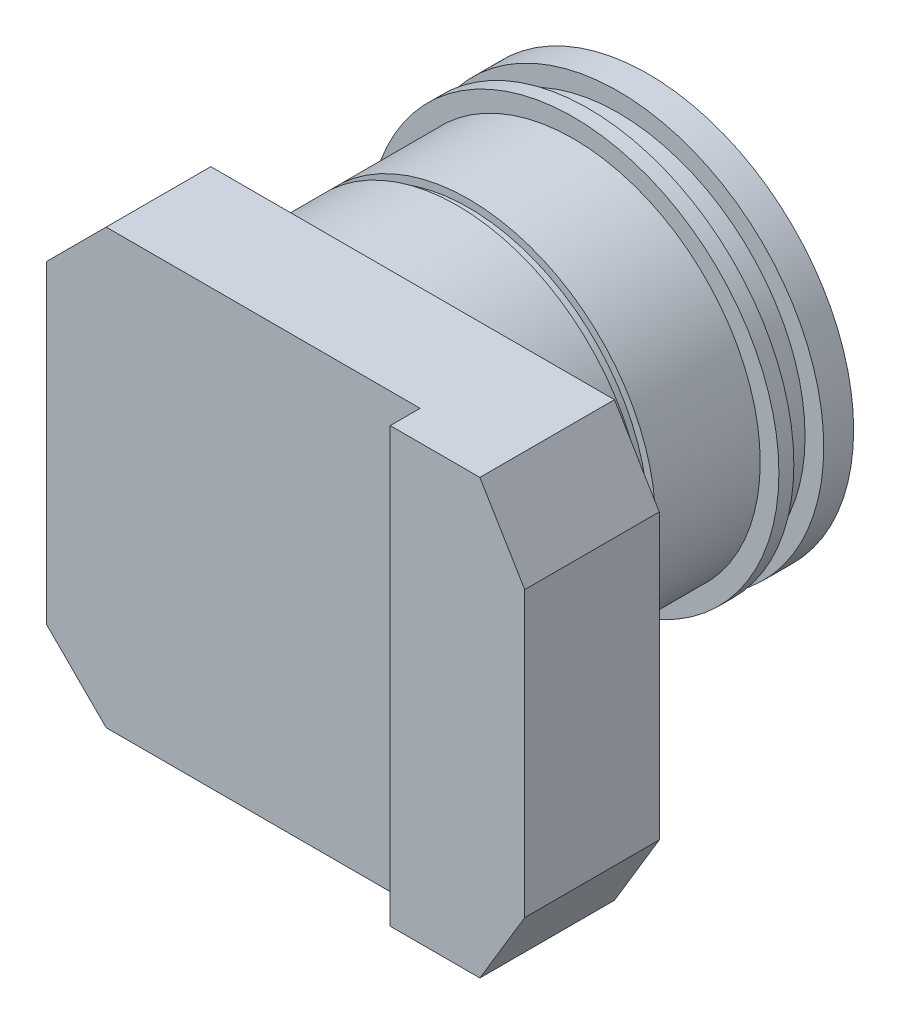
SolidWorks part; units mm, degrees
ref_plane "Front Plane" through (0, 0, 0) normal (0, 0, 1) x (1, 0, 0)
ref_plane "Top Plane" through (0, 0, 0) normal (0, 1, 0) x (1, 0, 0)
ref_plane "Right Plane" through (0, 0, 0) normal (1, 0, 0) x (0, 0, -1)
sketch "Sketch1" plane through (0, 0, 0) normal (0, 0, 1) x (1, 0, 0)
  line L1 (-17, 14.5) -> (17, 14.5)
  line L2 (-17, 14.5) -> (-17, -14.5)
  line L3 (-17, -14.5) -> (17, -14.5)
  line L4 (17, 14.5) -> (17, -14.5)
  line L5 (-17, 14.5) -> (17, -14.5) construction
  line L6 (-17, -14.5) -> (17, 14.5) construction
  point P0 (0, 0)
  dimension "D1" = 34
  dimension "D2" = 29
extrude "Boss-Extrude1" add sketch "Sketch1" along normal mid plane 7 contours L2 L3 L4 L1
sketch "Sketch2" plane through (0, 0, 3.5) normal (0, 0, 1) x (1, 0, 0)
  line L0 (-17, -14.5) -> (17, -14.5) construction
  line L1 (17, 14.5) -> (8, 14.5)
  line L2 (17, 14.5) -> (17, -14.5)
  line L3 (17, -14.5) -> (8, -14.5)
  line L4 (8, 14.5) -> (8, -14.5)
  dimension "D1" = 9
extrude "Boss-Extrude2" add sketch "Sketch2" along normal blind 2
sketch "Sketch3" plane through (0, 0, -3.5) normal (0, 0, -1) x (-1, 0, 0)
  line L0 (-14, -14.5) -> (-17, -9.5)
  line L1 (17, -14.5) -> (-17, -14.5) construction
  line L2 (-17, 14.5) -> (-17, -14.5) construction
  line L3 (-17, -9.5) -> (-17, -14.5)
  line L4 (-17, -14.5) -> (-14, -14.5)
  line L5 (13, -14.5) -> (17, -10.5)
  line L6 (17, 14.5) -> (17, -14.5) construction
  line L7 (17, -10.5) -> (17, -14.5)
  line L8 (17, -14.5) -> (13, -14.5)
  line L9 (17, 10.5) -> (13, 14.5)
  line L10 (17, 14.5) -> (-17, 14.5) construction
  line L11 (13, 14.5) -> (17, 14.5)
  line L12 (17, 14.5) -> (17, 10.5)
  line L13 (-17, 9.5) -> (-14, 14.5)
  line L14 (-14, 14.5) -> (-17, 14.5)
  line L15 (-17, 14.5) -> (-17, 9.5)
  dimension "D1" = 3
  dimension "D2" = 5
  dimension "D3" = 4
  dimension "D4" = 4
  dimension "D5" = 4
  dimension "D6" = 4
extrude "Cut-Extrude1" cut sketch "Sketch3" against normal through all
sketch "Sketch4" plane through (0, 0, 0) normal (0, 1, 0) x (1, 0, 0)
  line L0 (-17, 3.5) -> (-4.5, 3.5)
  line L1 (-17, 3.5) -> (-17, 11.5)
  line L2 (-17, 11.5) -> (-16.5, 11.5)
  line L3 (-16.5, 11.5) -> (-16.5, 12.25)
  line L4 (-16.5, 12.25) -> (-17, 12.25)
  line L5 (-17, 12.25) -> (-17, 19.25)
  line L6 (-17, 19.25) -> (-18.25, 19.25)
  line L7 (-18.25, 19.25) -> (-18.25, 20.25)
  line L8 (-18.25, 20.25) -> (-17, 20.25)
  line L9 (-17, 20.25) -> (-17, 22.25)
  line L10 (-17, 22.25) -> (-18.25, 22.25)
  line L11 (-18.25, 22.25) -> (-18.25, 24.25)
  line L12 (-18.25, 24.25) -> (-4.5, 24.25)
  line L13 (-17, 3.5) -> (8, 3.5) construction
  line L14 (-13, -3.5) -> (8, -3.5) construction
  line L15 (-4.5, 24.25) -> (-4.5, 3.5) construction
  line L16 (-4.5, 3.5) -> (-4.5, 24.25)
  dimension "D1" = 8
  dimension "D2" = 27.75
  dimension "D3" = 2
  dimension "D4" = 1
  dimension "D5" = 2
  dimension "D6" = 7
  dimension "D7" = 13.75
  dimension "D8" = 0.5
revolve "Revolve1" add sketch "Sketch4" angle 360 about L16
sketch "Sketch5" plane through (0, 0, -24.25) normal (0, 0, -1) x (-1, 0, 0)
  circle A0 centre (4.5, 0) radius 9.75
  circle A2 centre (4.5, 0) radius 13.75 construction
  dimension "D1" = 4
extrude "Cut-Extrude2" cut sketch "Sketch5" against normal blind 5 draft 45
sketch "Sketch6" plane through (0, 0, 0) normal (0, 1, 0) x (1, 0, 0)
  line L0 (-9.25, 19.25) -> (-4.5, 19.25)
  line L1 (-4.5, 19.25) -> (-4.5, 24)
  line L2 (0.25, 19.25) -> (-9.25, 19.25) construction
  line L3 (-14.25, 24.25) -> (-9.25, 19.25) construction
  line L4 (-9.25, 19.25) -> (0.25, 19.25) construction
  line L5 (0.25, 19.25) -> (5.25, 24.25) construction
  arc A0 (-9.25, 19.25) -> (-4.5, 24) centre (-4.5, 19.25) cw
  point P2 (17.0433, 19.25)
  point P4 (0, 19.25)
  point P9 (17.0433, 19.25)
  point P10 (-5.5124, 22.9876)
  point P11 (0, 0)
  point P14 (0, 0)
  point P16 (0, 19.25)
  point P17 (0, 0)
  point P18 (1.0828, 19.25)
  point P19 (0, 0)
  point P21 (0, 19.25)
  point P22 (0.25, 19.25)
revolve "Revolve2" add sketch "Sketch6" angle 360 about L1
